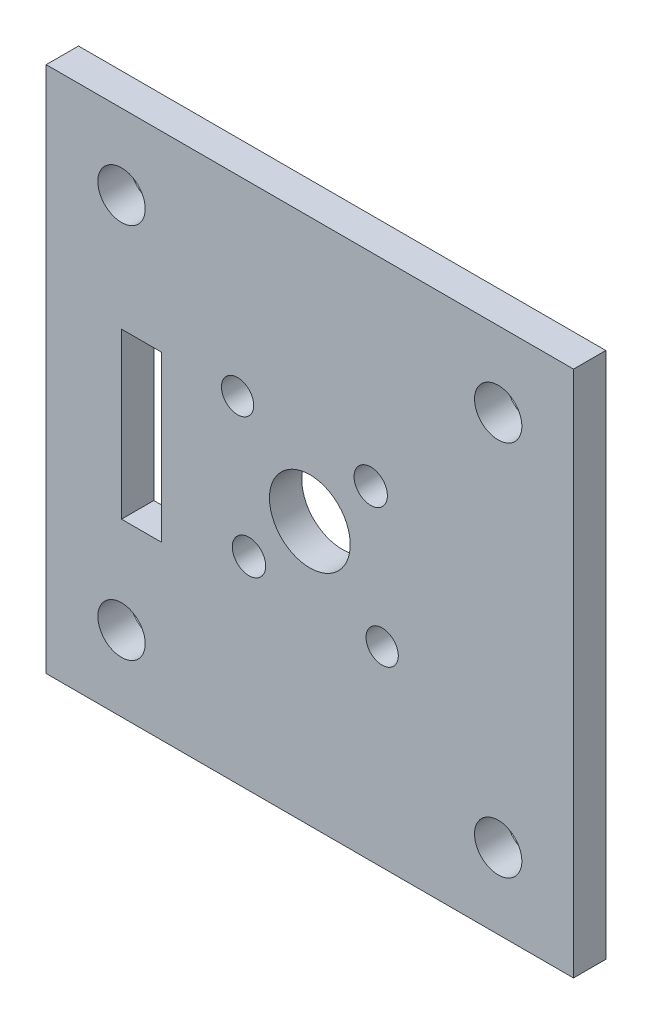
SolidWorks part; units mm, degrees
ref_plane "Front Plane" through (0, 0, 0) normal (0, 0, 1) x (1, 0, 0)
ref_plane "Top Plane" through (0, 0, 0) normal (0, 1, 0) x (1, 0, 0)
ref_plane "Right Plane" through (0, 0, 0) normal (1, 0, 0) x (0, 0, -1)
sketch "Sketch1" plane through (0, 0, 0) normal (0, 0, 1) x (1, 0, 0)
  line L0 (-17.5, 17.5) -> (17.5, 17.5) construction
  line L5 (-24.5, -24.5) -> (24.5, -24.5)
  line L6 (-24.5, -24.5) -> (-24.5, 24.5)
  line L11 (-24.5, 24.5) -> (24.5, 24.5)
  line L13 (24.5, -24.5) -> (24.5, 24.5)
  line L14 (-24.5, -24.5) -> (24.5, 24.5) construction
  line L15 (-24.5, 24.5) -> (24.5, -24.5) construction
  line L20 (-17.5, 17.5) -> (17.5, -17.5) construction
  line L22 (17.5, 17.5) -> (17.5, -17.5) construction
  line L23 (17.5, -17.5) -> (-17.5, -17.5) construction
  line L24 (-17.5, -17.5) -> (-17.5, 17.5) construction
  circle A8 centre (-17.5, 17.5) radius 2.2
  circle A9 centre (17.5, -17.5) radius 2.2
  circle A10 centre (17.5, 17.5) radius 2.2
  circle A11 centre (-17.5, -17.5) radius 2.2
  point P0 (0, 0)
  point P16 (-0.5896, 0.5896)
  dimension "D3" = 4.4
  dimension "D4" = 4.4
  dimension "D5" = 4.4
  dimension "D6" = 4.4
  dimension "D7" = 35
  dimension "D1" = 49
  dimension "D2" = 49
extrude "Boss-Extrude1" add sketch "Sketch1" along normal blind 3 contours L5 L13 L11 L6 A11 A10 A9 A8 region at (0, 0, 0)
sketch "Sketch2" plane through (0, 0, 0) normal (0, 0, -1) x (-1, 0, 0)
  line L0 (-17.5, 17.5) -> (17.5, -17.5) construction
  line L1 (17.5, 17.5) -> (-17.5, -17.5) construction
  line L3 (13.8005, 6.7175) -> (17.5, 6.7175)
  line L4 (13.8005, 6.7175) -> (13.8005, -8.5767)
  line L5 (13.8005, -8.5767) -> (17.5, -8.5767)
  line L6 (17.5, 6.7175) -> (17.5, -8.5767)
  line L7 (13.8005, 6.7175) -> (17.5, -8.5767) construction
  line L8 (13.8005, -8.5767) -> (17.5, 6.7175) construction
  circle A0 centre (-5.6569, 5.6569) radius 1.55
  circle A1 centre (6.7175, 6.7175) radius 1.5
  circle A2 centre (5.6569, -5.6569) radius 1.55
  circle A3 centre (-6.7175, -6.7175) radius 1.5
  circle A4 centre (0, 0) radius 3.7536
  point P23 (15.6503, -0.9296)
  dimension "D1" = 3.1
  dimension "D2" = 3.1
  dimension "D3" = 3
  dimension "D4" = 3
  dimension "D5" = 19
  dimension "D6" = 16
extrude "Cut-Extrude1" cut sketch "Sketch2" against normal blind 3
